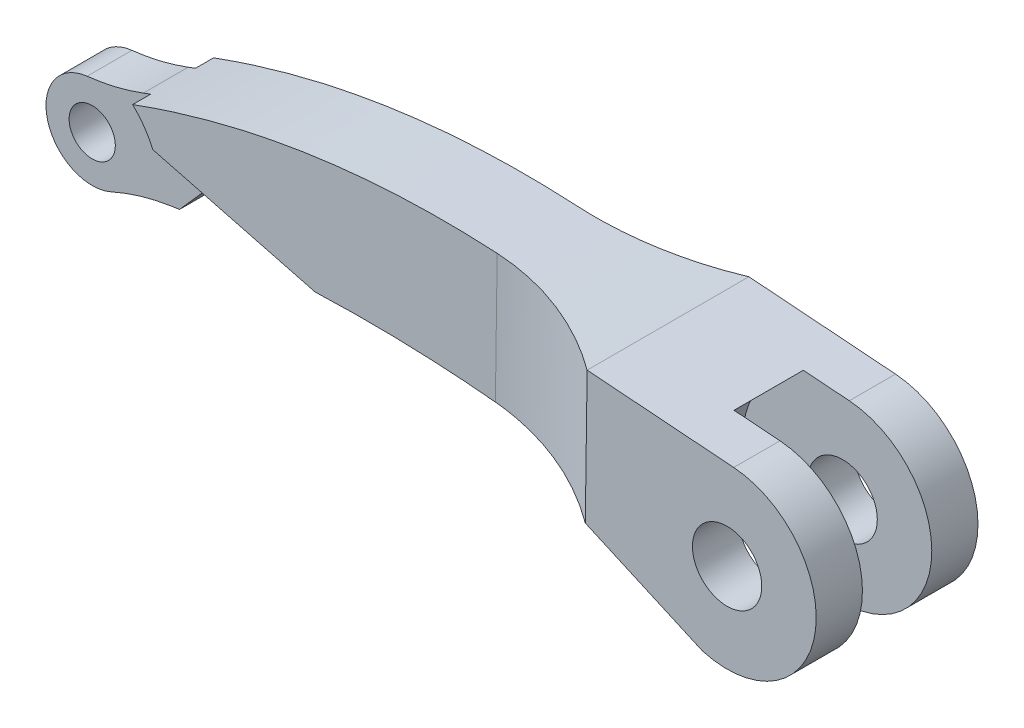
SolidWorks part; units mm, degrees
note: The reader was unsure of these and kept them because the rebuilt part matched: shared geometry of "Sketch4<2>", "Sketch5<2>".
ref_plane "Спереди" through (0, 0, 0) normal (0, 0, 1) x (1, 0, 0)
ref_plane "Сверху" through (0, 0, 0) normal (0, 1, 0) x (1, 0, 0)
ref_plane "Справа" through (0, 0, 0) normal (1, 0, 0) x (0, 0, -1)
sketch "Sketch1" plane through (0, 0, 0) normal (0, 0, 1) x (1, 0, 0)
  line L2 (0, 0) -> (1, 0) construction
  line L3 (1.4353, -1.3928) -> (15.4492, 1.1857) construction
  line L4 (15.4492, 1.1857) -> (28.4491, -2.568) construction
  line L5 (0.5799, 1.9141) -> (13.95, 7.6491) construction
  line L6 (13.95, 7.6491) -> (29.5304, 2.963) construction
  circle A0 centre (0, 0) radius 1
  arc A2 (28.4491, -2.568) -> (29.5304, 2.963) centre (30, 0) ccw
  circle A3 centre (30, 0) radius 1.5
  arc A4 (0.5799, 1.9141) -> (1.4353, -1.3928) centre (0, 0) ccw
  spline S0 degree 2 poles (1.4353, -1.3928) (15.4492, 1.1857) (28.4491, -2.568) knots 0 0 0 1 1 1
  spline S1 degree 2 poles (0.5799, 1.9141) (13.95, 7.6491) (29.5304, 2.963) knots 0 0 0 1 1 1
  dimension "D4" = 2
  dimension "D6" = 3
  dimension "D7" = 6
  dimension "D1" = 2
  dimension "D2" = 30
extrude "Boss-Extrude1" add sketch "Sketch1" along normal mid plane 3.5
fillet "Fillet1" radius 3 1 edges at (29.5304, 2.963, 0)
sketch "Sketch2" plane through (0, 0, 0) normal (0, 0, 1) x (1, 0, 0)
  line L0 (30.2881, 3.8462) -> (23.9444, 4.3213)
  line L1 (23.9444, 4.3213) -> (23.8653, -1.4476)
  line L2 (23.8653, -1.4476) -> (28.9253, -3.7042)
  circle A0 centre (30, 0) radius 1.5
  circle A1 centre (30, 0) radius 1.5 construction
  arc A2 (28.9253, -3.7042) -> (30.2881, 3.8462) centre (30, 0) ccw
  parabola Q0 (29.0095, 3.1169) -> (0.5799, 1.9141) focus (11.8214, -14.4675) apex (7.8561, 4.2292) construction
  parabola Q1 (1.4353, -1.3928) -> (28.4491, -2.568) focus (17.2415, -28.8256) apex (21.6887, -1.055) construction
extrude "Boss-Extrude2" add sketch "Sketch2" along normal mid plane 7
sketch "Sketch3" plane through (0, 0, 0) normal (0, 0, 1) x (1, 0, 0)
  circle A0 centre (30, 0) radius 4.342
extrude "Cut-Extrude1" cut sketch "Sketch3" against normal mid plane 3
fillet "Fillet2" radius 10 2 edges at (23.9049, 1.4369, -1.75) (23.9049, 1.4369, 1.75)
fillet "Fillet3" radius 10 2 edges at (0.5799, 1.9141, 0) (1.4353, -1.3928, 0)
sketch "Sketch4" plane through (0, 0, 1.75) normal (0, 0, 1) x (1, 0, 0)
  circle A0 centre (0, 0) radius 3.692
extrude "Cut-Extrude2" cut sketch "Sketch4" against normal blind 0.78
extrude "Cut-Extrude3" cut sketch "Sketch4<2>" along normal blind 0.78 from surface at -3.5 starting at face at (1, 0, -1.75)
sketch "Sketch4<2>" plane through (0, 0, 1.75) normal (0, 0, 1) x (1, 0, 0) same geometry as "Sketch4"
sketch "Sketch5" plane through (0, 0, -1.75) normal (0, 0, -1) x (-1, 0, 0)
  line L0 (-3.4008, 1.4372) -> (-10.4244, -0.3861)
  line L1 (-10.4244, -0.3861) -> (-1.8373, -1.8892)
  line L2 (-1.8373, -1.8892) -> (-3.4008, 1.4372)
  arc A0 (-2.5285, 2.6902) -> (-3.5425, -1.04) centre (0, 0) ccw construction
  parabola Q0 (-3.5425, -1.04) -> (-18.2249, -0.61) focus (-17.2415, -28.8256) apex (-21.6887, -1.055) construction
extrude "Cut-Extrude4" cut sketch "Sketch5" against normal up to surface (0.78 mm away) up to face at (1, 0, -0.97)
extrude "Cut-Extrude5" cut sketch "Sketch5<2>" against normal up to surface (0.78 mm away) from surface
sketch "Sketch5<2>" plane through (0, 0, -1.75) normal (0, 0, -1) x (-1, 0, 0) same geometry as "Sketch5"
sketch "Sketch6" plane through (0, 0, -0.97) normal (0, 0, -1) x (-1, 0, 0)
  line L0 (-3.7781, -1.0049) -> (-5.1299, 0.5227)
  line L1 (-5.1299, 0.5227) -> (-8.4289, -0.4957)
  line L3 (-3.7781, -1.0049) -> (-5.9846, -1.2361)
  line L4 (-5.9846, -1.2361) -> (-8.4289, -0.4957)
  parabola Q0 (-3.4069, -1.0606) -> (-10.4244, -0.3861) focus (-17.2415, -28.8256) apex (-21.6887, -1.055) construction
  parabola Q1 (-3.4069, -1.0606) -> (-10.4244, -0.3861) focus (-17.2415, -28.8256) apex (-21.6887, -1.055) construction
  parabola Q2 (-3.4069, -1.0606) -> (-10.4244, -0.3861) focus (-17.2415, -28.8256) apex (-21.6887, -1.055) construction
extrude "Cut-Extrude6" cut sketch "Sketch6" against normal blind 2
